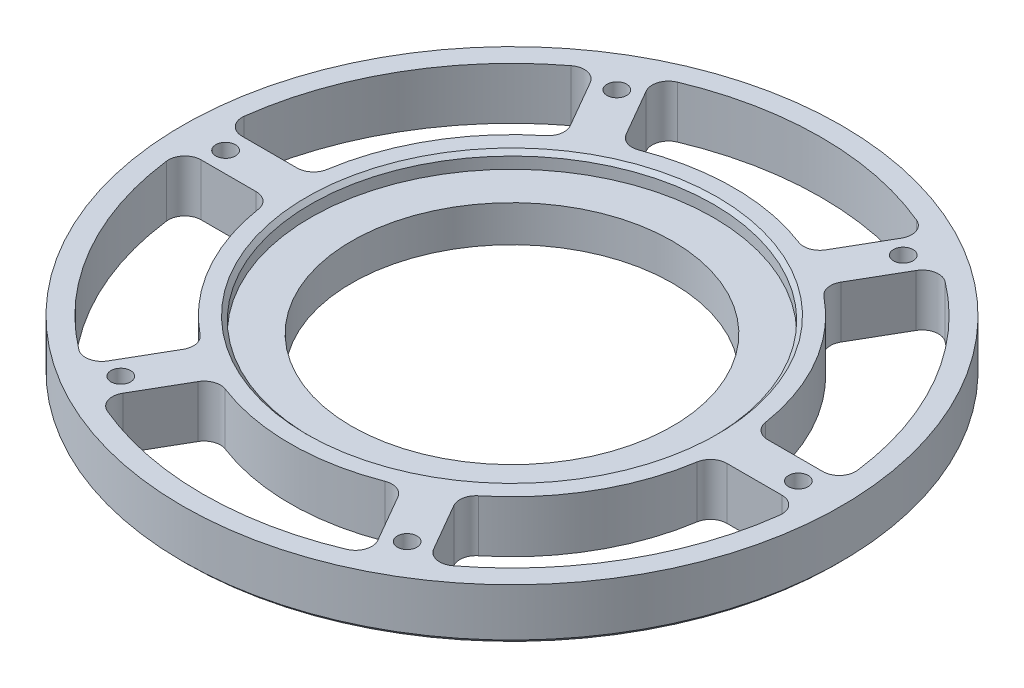
SolidWorks part; units mm, degrees
material "6061-T6 (SS)"
ref_plane "Front Plane" through (0, 0, 0) normal (0, 0, 1) x (1, 0, 0)
ref_plane "Top Plane" through (0, 0, 0) normal (0, 1, 0) x (1, 0, 0)
ref_plane "Right Plane" through (0, 0, 0) normal (1, 0, 0) x (0, 0, -1)
sketch "Sketch2" plane through (0, 0, 0) normal (1, 0, 0) x (0, 0, -1)
  line L0 (-39.2125, 0) -> (-80.55, 0)
  line L1 (-80.55, 0) -> (-80.55, 12.7)
  line L2 (-80.55, 12.7) -> (-49.2125, 12.7)
  line L3 (-49.2125, 12.7) -> (-49.2125, 8.9)
  line L4 (-49.2125, 8.9) -> (-39.2125, 8.9)
  line L5 (-39.2125, 8.9) -> (-39.2125, 0)
  dimension "D1" = 80.55
  dimension "D2" = 12.7
  dimension "D4" = 49.2125
  dimension "D5" = 10
  dimension "D3" = 8.9
ref_axis "Axis1" through (0, -0.635, 0) along (0, 1, 0)
revolve "Revolve1" add sketch "Sketch2" angle 360 about axis through (0, -0.635, 0) along (0, 1, 0)
hole_wizard "#12 (0.189) Diameter Hole1" positions "Sketch6" profile "Sketch7" hole size "#12" standard "ANSI Inch" end condition through all
sketch "Sketch6" plane through (0, 12.7, 0) normal (0, 1, 0) x (1, 0, 0)
  line L0 (0, 0) -> (-69.8201, 120.932) construction
  line L2 (0, 0) -> (0, 109.0908) construction
  point P0 (-35, 60.6218)
  dimension "D1" = 30
  dimension "D2" = 70
sketch "Sketch7" plane through (-35, 12.7, -60.6218) normal (1, 0, 0) x (0, 0, 1)
  line L0 (0, 0) -> (0, 12.7)
  line L1 (0, 12.7) -> (2.4003, 12.7)
  line L2 (2.4003, 12.7) -> (2.4003, 0)
  line L5 (2.4003, 0) -> (0, 0)
  line L11 (0, -6.35) -> (0, 107.95) construction
  dimension "Thru Hole Dia." = 4.8006
  dimension "Thru Hole Depth" = 12.7
pattern_circular "CirPattern3" count 6 over 360 about axis through (0, -0.635, 0) along (0, 1, 0) of "#12 (0.189) Diameter Hole1"
sketch "Sketch8" plane through (0, 12.7, 0) normal (0, 1, 0) x (1, 0, 0)
  line L0 (-33.3621, 67.7848) -> (-22.6606, 49.2493)
  line L1 (33.3621, 67.7848) -> (22.6606, 49.2493)
  line L2 (0, 0) -> (-35, 60.6218) construction
  line L4 (0, 0) -> (0, 93.9995) construction
  arc A0 (-22.6606, 49.2493) -> (22.6606, 49.2493) centre (0, 0) cw
  arc A1 (-33.3621, 67.7848) -> (33.3621, 67.7848) centre (0, 0) cw
  circle A2 centre (0, 0) radius 49.2125 construction
  circle A3 centre (0, 0) radius 80.55 construction
  dimension "D1" = 5
  dimension "D2" = 5
  dimension "D3" = 5
extrude "Cut-Extrude1" cut sketch "Sketch8" against normal through all
fillet "Fillet1" radius 4 4 edges at (33.3621, 6.35, -67.7848) (22.6606, 6.35, -49.2493) (-33.3621, 6.35, -67.7848) (-22.6606, 6.35, -49.2493)
pattern_circular "CirPattern4" count 6 over 360 about axis through (0, -0.635, 0) along (0, 1, 0) of "Cut-Extrude1", "Fillet1"
chamfer "Chamfer1" distance 1 angle 45 1 edges at (0, 12.7, -49.2125)
chamfer "Chamfer2" distance 1 angle 45 1 edges at (0, 0, -80.55)
equation "\"TubeDiameter\" = 6.500in"
equation "\"D1@Sketch2\"=(\"TubeDiameter\"-4)/2"
